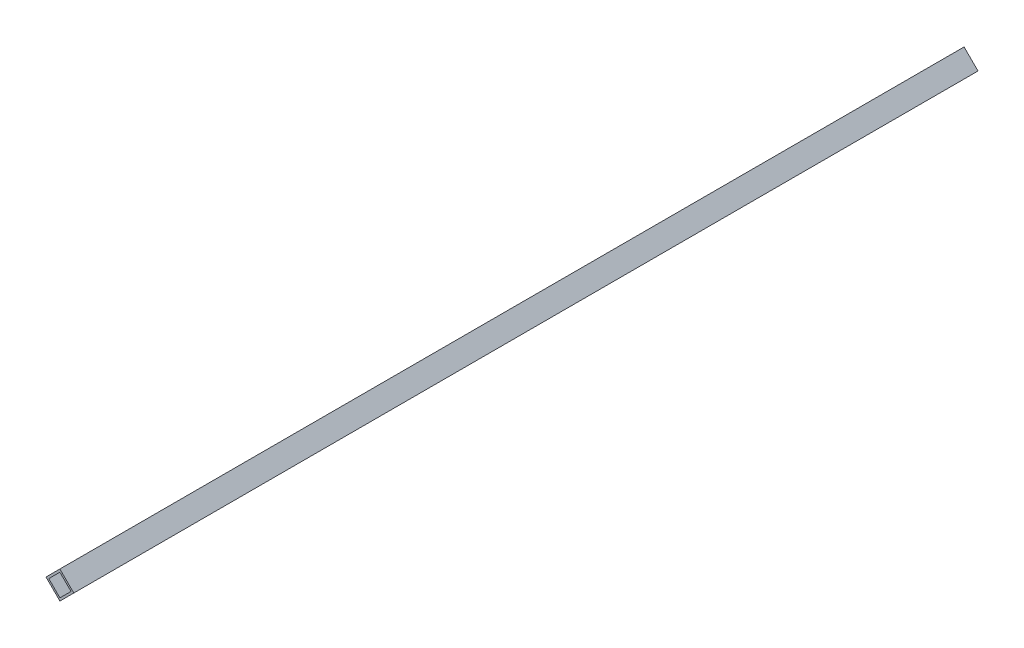
SolidWorks part; units mm, degrees
material "AlMg3 "
ref_plane "xy" through (0, 0, 0) normal (0, 0, 1) x (1, 0, 0)
ref_plane "xz" through (0, 0, 0) normal (0, 1, 0) x (1, 0, 0)
ref_plane "yz" through (0, 0, 0) normal (1, 0, 0) x (0, 0, -1)
ref_axis "x" through (-7.7782, 0, 0) along (1, 0, 0)
ref_axis "y" through (0, 7.7782, 0) along (0, -1, 0)
ref_axis "z" through (0, 0, -275) along (0, 0, 1)
sketch "Sketch1" plane through (0, 0, 0) normal (0, 0, 1) x (1, 0, 0)
  line L1 (0, -7.0711) -> (7.0711, 0)
  line L2 (7.0711, 0) -> (0, 7.0711)
  line L3 (0, 7.0711) -> (-7.0711, 0)
  line L4 (-7.0711, 0) -> (0, -7.0711)
  circle A0 centre (0, 0) radius 5 construction
  dimension "D1" = 10
extrude "Extrude-Thin1" add sketch "Sketch1" along normal mid plane 460 thin thin type one direction reverse wall 1
